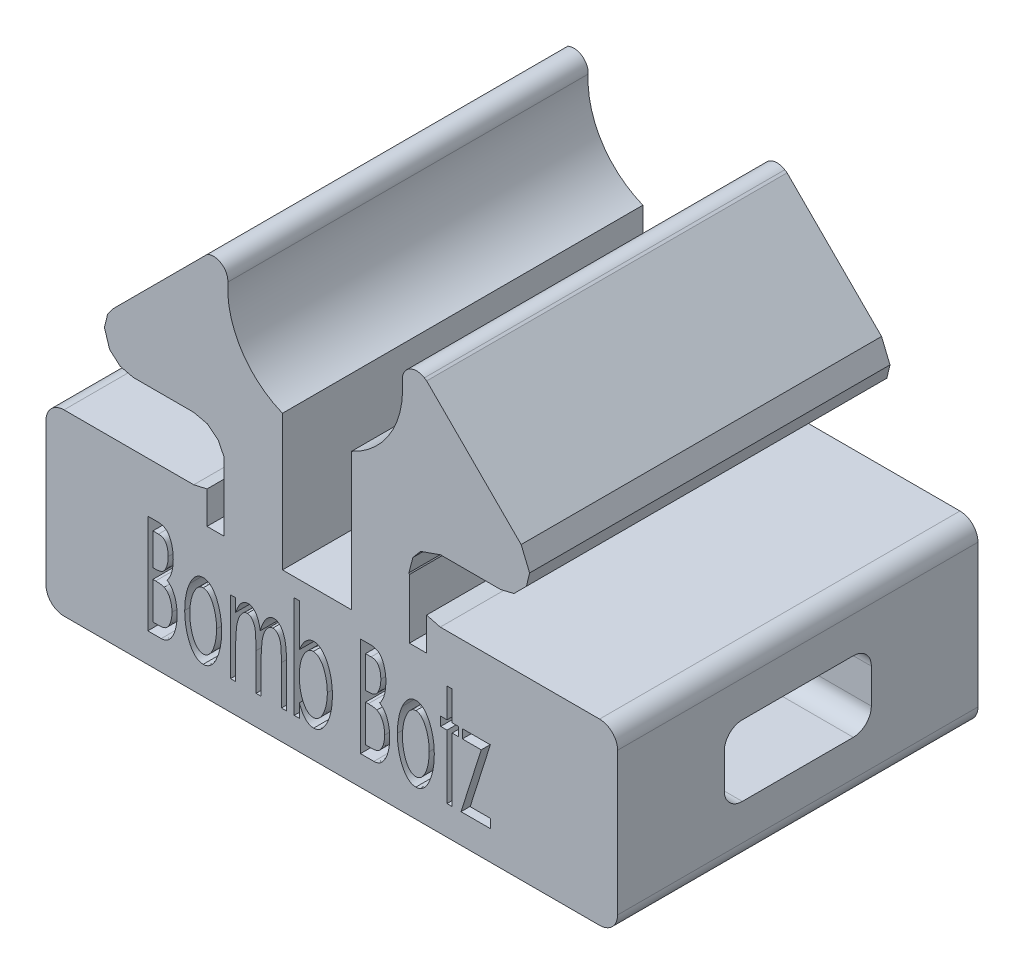
SolidWorks part; units mm, degrees
ref_plane "Front Plane" through (0, 0, 0) normal (0, 0, 1) x (1, 0, 0)
ref_plane "Top Plane" through (0, 0, 0) normal (0, 1, 0) x (1, 0, 0)
ref_plane "Right Plane" through (0, 0, 0) normal (1, 0, 0) x (0, 0, -1)
sketch "Sketch5" plane through (0, 0, 0) normal (0, 0, 1) x (1, 0, 0)
  line L0 (-6.4748, -10.4902) -> (-6.9383, -10.3783)
  line L1 (-6.9383, -10.3783) -> (-7.3088, -10.0545)
  line L2 (-7.3088, -10.0545) -> (-7.4908, -9.4742)
  line L3 (-7.4908, -9.4742) -> (-7.3789, -9.0107)
  line L4 (-7.3789, -9.0107) -> (-7.1932, -8.7558)
  line L5 (-7.1932, -8.7558) -> (-3.8632, -5.4257)
  line L6 (-3.8632, -5.4257) -> (-2.8331, -4.7375)
  line L7 (-2.8331, -4.7375) -> (-1.6181, -4.4958)
  line L8 (-1.6181, -4.4958) -> (1.6181, -4.4958)
  line L9 (1.6181, -4.4958) -> (2.6682, -4.6745)
  line L10 (2.6682, -4.6745) -> (3.8632, -5.4257)
  line L11 (3.8632, -5.4257) -> (7.1932, -8.7558)
  line L12 (7.1932, -8.7558) -> (7.4908, -9.4742)
  line L13 (7.4908, -9.4742) -> (7.3789, -9.9377)
  line L14 (6.4748, -10.4902) -> (6.9383, -10.3783)
  line L15 (6.9383, -10.3783) -> (7.3789, -9.9377)
  line L16 (6.4748, -10.4902) -> (4.3434, -10.4902)
  line L19 (-6.4748, -10.4902) -> (-4.3434, -10.4902)
  line L20 (-4.3434, -10.4902) -> (-3.8632, -10.6)
  line L21 (-3.8632, -10.6) -> (-3.486, -10.8982)
  line L22 (-3.486, -10.8982) -> (-3.2711, -11.3288)
  line L23 (-3.2711, -11.3288) -> (-3.2711, -11.8614)
  line L24 (-3.2711, -11.8614) -> (-3.486, -12.292)
  line L25 (-3.486, -12.292) -> (-3.8632, -12.5902)
  line L26 (-3.8632, -12.5902) -> (-4.3434, -12.7)
  line L27 (-4.3434, -12.7) -> (-9.5504, -12.7)
  line L28 (-9.5504, -12.7) -> (-9.5504, -18.9956)
  line L29 (-9.5504, -18.9956) -> (10.5918, -18.9956)
  line L30 (10.5918, -18.9956) -> (10.5918, -12.7)
  line L31 (10.5918, -12.7) -> (4.3434, -12.7)
  line L32 (4.3434, -12.7) -> (3.8076, -12.5614)
  line L33 (3.8076, -12.5614) -> (3.486, -12.292)
  line L34 (3.486, -12.292) -> (3.2385, -11.5951)
  line L35 (3.2385, -11.5951) -> (3.3771, -11.0593)
  line L36 (3.3771, -11.0593) -> (3.6465, -10.7377)
  line L37 (3.6465, -10.7377) -> (4.3434, -10.4902)
  point P46 (0, 0)
  point P57 (0, 0)
  point P58 (0, 0)
  point P59 (0, 0)
  point P60 (0, 0)
extrude "Boss-Extrude1" add sketch "Sketch5" against normal blind 12.7
sketch "Sketch10" plane through (0, 0, 0) normal (0, 0, 1) x (1, 0, 0)
  circle A0 centre (-0.0665, -6.096) radius 3.0821
extrude "Cut-Extrude1" cut sketch "Sketch10" against normal through all
sketch "Sketch11" plane through (0, 0, 0) normal (0, 0, 1) x (1, 0, 0)
  line L1 (-1.2179, -5.8277) -> (1.2179, -5.8277)
  line L2 (-1.2179, -5.8277) -> (-1.2179, -13.7361)
  line L3 (-1.2179, -13.7361) -> (1.2179, -13.7361)
  line L4 (1.2179, -5.8277) -> (1.2179, -13.7361)
  line L5 (-1.2179, -5.8277) -> (1.2179, -13.7361) construction
  line L6 (-1.2179, -13.7361) -> (1.2179, -5.8277) construction
  point P0 (0, -9.7819)
extrude "Cut-Extrude2" cut sketch "Sketch11" against normal through all
sketch "Sketch13" plane through (-9.5504, 0, 0) normal (-1, 0, 0) x (0, 0, 1)
  line L1 (-8.941, -14.6031) -> (-3.759, -14.6031)
  line L2 (-8.941, -14.6031) -> (-8.941, -17.0925)
  line L3 (-8.941, -17.0925) -> (-3.759, -17.0925)
  line L4 (-3.759, -14.6031) -> (-3.759, -17.0925)
  line L5 (-8.941, -14.6031) -> (-3.759, -17.0925) construction
  line L6 (-8.941, -17.0925) -> (-3.759, -14.6031) construction
  point P0 (-6.35, -15.8478)
extrude "Cut-Extrude4" cut sketch "Sketch13" against normal through all
fillet "Fillet1" radius 0.635 1 edges at (-9.5504, -12.7, -6.35)
fillet "Fillet2" radius 0.635 7 edges at (10.5918, -18.9956, -6.35) (10.5918, -12.7, -6.35) (0.5207, -14.6031, -3.759) (-9.5504, -18.9956, -6.35) (0.5207, -17.0925, -3.759) (0.5207, -17.0925, -8.941) (0.5207, -14.6031, -8.941)
fillet "Fillet3" radius 0.508 2 edges at (2.6682, -4.6745, -6.35) (-2.8331, -4.7375, -6.35)
sketch "Sketch15" plane through (0, 0, 0) normal (0, 0, 1) x (1, 0, 0)
  text T0 "Bomb Botz" font "Century Gothic" height 3.5
extrude "Cut-Extrude5" cut sketch "Sketch15" against normal blind 1.27
sketch "Sketch17" plane through (0, 0, 0) normal (0, 0, 1) x (1, 0, 0)
  line L0 (3.486, -12.292) -> (3.2385, -11.5951) construction
  line L1 (3.2547, -11.6407) -> (3.8597, -11.6407)
  line L2 (3.2547, -11.6407) -> (3.2547, -13.7361)
  line L3 (3.2547, -13.7361) -> (3.8597, -13.7361)
  line L4 (3.8597, -11.6407) -> (3.8597, -13.7361)
  line L5 (-3.2711, -11.3288) -> (-3.2711, -11.8614) construction
  line L6 (-3.2711, -11.5951) -> (-3.8755, -11.5951)
  line L7 (-3.2711, -11.5951) -> (-3.2711, -13.7361)
  line L8 (-3.2711, -13.7361) -> (-3.8755, -13.7361)
  line L9 (-3.8755, -11.5951) -> (-3.8755, -13.7361)
extrude "Cut-Extrude7" cut sketch "Sketch17" against normal through all
